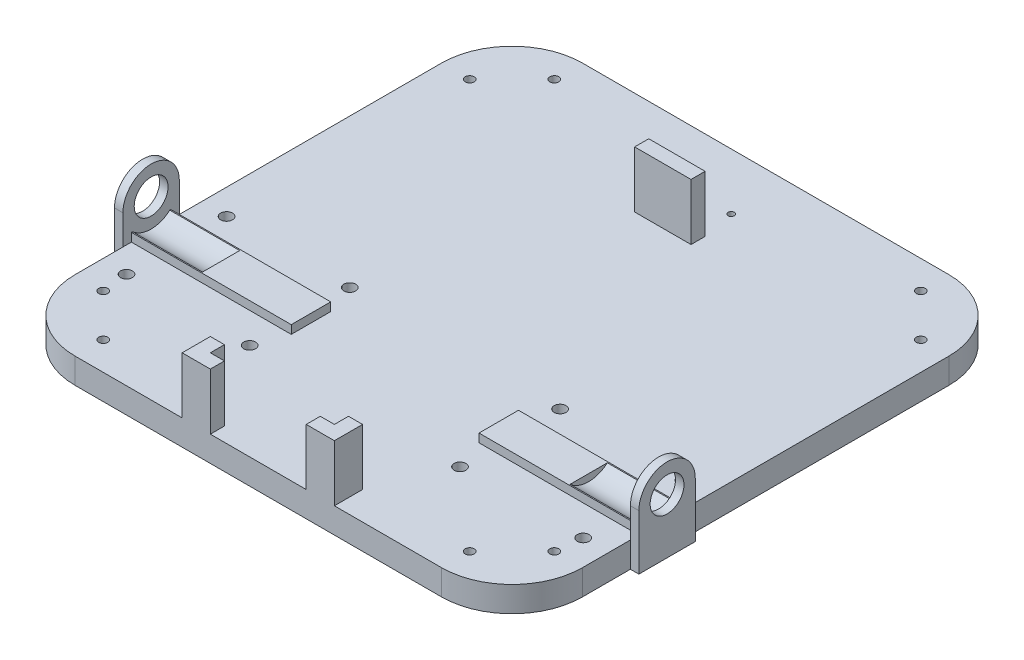
SolidWorks part; units mm, degrees
ref_plane "Front Plane" through (0, 0, 0) normal (0, 0, 1) x (1, 0, 0)
ref_plane "Top Plane" through (0, 0, 0) normal (0, 1, 0) x (1, 0, 0)
ref_plane "Right Plane" through (0, 0, 0) normal (1, 0, 0) x (0, 0, -1)
sketch "Sketch1" plane through (0, 0, 0) normal (0, 1, 0) x (1, 0, 0)
  line L1 (-65, -90) -> (65, -90)
  line L2 (-90, -65) -> (-90, 65)
  line L3 (-65, 90) -> (65, 90)
  line L4 (90, -65) -> (90, 65)
  arc A0 (-90, 65) -> (-65, 90) centre (-65, 65) cw
  arc A1 (65, 90) -> (90, 65) centre (65, 65) cw
  arc A2 (90, -65) -> (65, -90) centre (65, -65) cw
  arc A3 (-65, -90) -> (-90, -65) centre (-65, -65) cw
  point P4 (-90, 0)
  point P6 (0, 90)
  dimension "D3" = 25
  dimension "D1" = 180
  dimension "D2" = 180
extrude "Plate" add sketch "Sketch1" along normal blind 9
sketch "Sketch2" plane through (0, 9, 0) normal (0, 1, 0) x (1, 0, 0)
  line L0 (-7.747, 70) -> (7.747, 70) construction
  line L1 (0, 90) -> (0, 70) construction
  line L2 (-65, 90) -> (65, 90) construction
  circle A1 centre (-7.747, 70) radius 1.09
  circle A2 centre (7.747, 70) radius 1.09
  dimension "D3" = 2.18
  dimension "D1" = 15.494
  dimension "D2" = 20
extrude "Caster Holes" cut sketch "Sketch2" against normal through all
sketch "Sketch3" plane through (0, 9, 0) normal (0, 1, 0) x (1, 0, 0)
  line L0 (-65, 90) -> (-65, -90) construction
  line L1 (65, 90) -> (65, -90) construction
  line L2 (-90, 65) -> (90, 65) construction
  line L3 (-90, -65) -> (90, -65) construction
  circle A0 centre (-65, 80) radius 1.6
  circle A1 centre (-80, 65) radius 1.6
  circle A2 centre (80, 65) radius 1.6
  circle A3 centre (80, -65) radius 1.6
  circle A4 centre (65, 80) radius 1.6
  circle A5 centre (65, -80) radius 1.6
  circle A6 centre (-65, -80) radius 1.6
  circle A7 centre (-80, -65) radius 1.6
  dimension "D1" = 3.2
  dimension "D2" = 15
  dimension "D3" = 15
  dimension "D4" = 15
  dimension "D5" = 15
  dimension "D6" = 15
  dimension "D7" = 15
  dimension "D8" = 15
  dimension "D9" = 15
extrude "Hex Holes" cut sketch "Sketch3" against normal through all
sketch "Sketch4" plane through (0, 9, 0) normal (0, 1, 0) x (1, 0, 0)
  line L0 (-27, -90) -> (-27, -80)
  line L1 (-65, -90) -> (65, -90) construction
  line L2 (-27, -80) -> (-22, -80)
  line L3 (-22, -80) -> (-22, -85)
  line L4 (-22, -85) -> (-17, -85)
  line L5 (-17, -85) -> (-17, -90)
  line L6 (-17, -90) -> (-27, -90)
  line L7 (17, -90) -> (17, -85)
  line L8 (17, -85) -> (22, -85)
  line L9 (22, -85) -> (22, -80)
  line L10 (22, -80) -> (27, -80)
  line L11 (27, -80) -> (27, -90)
  line L12 (27, -90) -> (17, -90)
  line L13 (-10, 58.5) -> (10, 58.5)
  line L14 (10, 58.5) -> (10, 53.5)
  line L15 (10, 53.5) -> (-10, 53.5)
  line L16 (-10, 53.5) -> (-10, 58.5)
  line L17 (-90, -65) -> (-90, 65) construction
  point P20 (0, 53.5)
  dimension "D1" = 5
  dimension "D2" = 44
  dimension "D3" = 63
  dimension "D4" = 20
  dimension "D5" = 5
  dimension "D6" = 138.5
extrude "Battery Holder" add sketch "Sketch4" along normal blind 20
sketch "Sketch5" plane through (0, 9, 0) normal (0, 1, 0) x (1, 0, 0)
  line L0 (-90, -65) -> (-90, 65) construction
  line L1 (-90, -45) -> (-33.3, -45)
  line L2 (-90, -45) -> (-90, -31)
  line L3 (-90, -31) -> (-33.3, -31)
  line L4 (-33.3, -45) -> (-33.3, -31)
  line L5 (90, -65) -> (90, 65) construction
  line L6 (90, -45) -> (33.3, -45)
  line L7 (90, -45) -> (90, -31)
  line L8 (90, -31) -> (33.3, -31)
  line L9 (33.3, -45) -> (33.3, -31)
  line L10 (-65, -90) -> (65, -90) construction
  dimension "D1" = 14
  dimension "D2" = 45
  dimension "D3" = 56.7
extrude "Boss-Extrude2" add sketch "Sketch5" along normal blind 3
sketch "Sketch6" plane through (-90, 0, 0) normal (-1, 0, 0) x (0, 0, 1)
  line L0 (31, 12) -> (45, 12) construction
  line L1 (45, 9) -> (65, 9) construction
  circle A0 centre (38, 19.5) radius 10
  point P5 (38, 12)
  dimension "D1" = 20
  dimension "D2" = 10.5
extrude "Cut-Extrude1" cut sketch "Sketch6" against normal blind 24.8
sketch "Sketch7" plane through (90, 0, 0) normal (1, 0, 0) x (0, 0, -1)
  line L0 (-31, 9) -> (65, 9) construction
  line L1 (-45, 12) -> (-31, 12) construction
  circle A0 centre (-38, 19.5) radius 10
  point P6 (-38, 12)
  dimension "D1" = 20
  dimension "D2" = 10.5
extrude "Cut-Extrude2" cut sketch "Sketch7" against normal blind 24.8
sketch "Sketch8" plane through (90, 0, 0) normal (1, 0, 0) x (0, 0, -1)
  line L0 (-48, 19.5) -> (-48, 0)
  line L1 (-65, 0) -> (65, 0) construction
  line L2 (-48, 0) -> (-28, 0)
  line L3 (-28, 19.5) -> (-28, 0)
  arc A2 (-28, 19.5) -> (-48, 19.5) centre (-38, 19.5) ccw
  circle A3 centre (-38, 19.5) radius 6
  dimension "D1" = 12
  dimension "D2" = 10
  dimension "D3" = 20
extrude "Boss-Extrude4" add sketch "Sketch8" along normal blind 3
sketch "Sketch9" plane through (-90, 0, 0) normal (-1, 0, 0) x (0, 0, 1)
  line L0 (28, 19.5) -> (28, 0)
  line L1 (65, 0) -> (-65, 0) construction
  line L2 (28, 0) -> (48, 0)
  line L3 (48, 0) -> (48, 19.5)
  circle A0 centre (38, 19.5) radius 6
  arc A1 (48, 19.5) -> (28, 19.5) centre (38, 19.5) ccw
  dimension "D1" = 12
extrude "Boss-Extrude5" add sketch "Sketch9" along normal blind 3
sketch "Sketch10" plane through (0, 9, 0) normal (0, 1, 0) x (1, 0, 0)
  line L0 (90, -65) -> (90, 65) construction
  line L1 (-90, -65) -> (-90, 65) construction
  circle A0 centre (81, -55.75) radius 2.1
  circle A1 centre (81, -20.25) radius 2.1
  circle A2 centre (-81, -20.25) radius 2.1
  circle A3 centre (-81, -55.75) radius 2.1
  circle A4 centre (-37.3, -20.25) radius 2.1
  circle A5 centre (-37.3, -55.75) radius 2.1
  circle A6 centre (37.3, -55.75) radius 2.1
  circle A7 centre (37.3, -20.25) radius 2.1
  point P17 (0, 0)
  point P18 (-39.0934, -62.7785)
  point P23 (0, 0)
  point P24 (0, 0)
  point P25 (0, 0)
  dimension "D2" = 4.2
  dimension "D1" = 9.25
  dimension "D3" = 9
  dimension "D4" = 35.5
  dimension "D5" = 9
  dimension "D6" = 43.7
  dimension "D7" = 43.7
extrude "Clamp Holes" cut sketch "Sketch10" against normal through all
